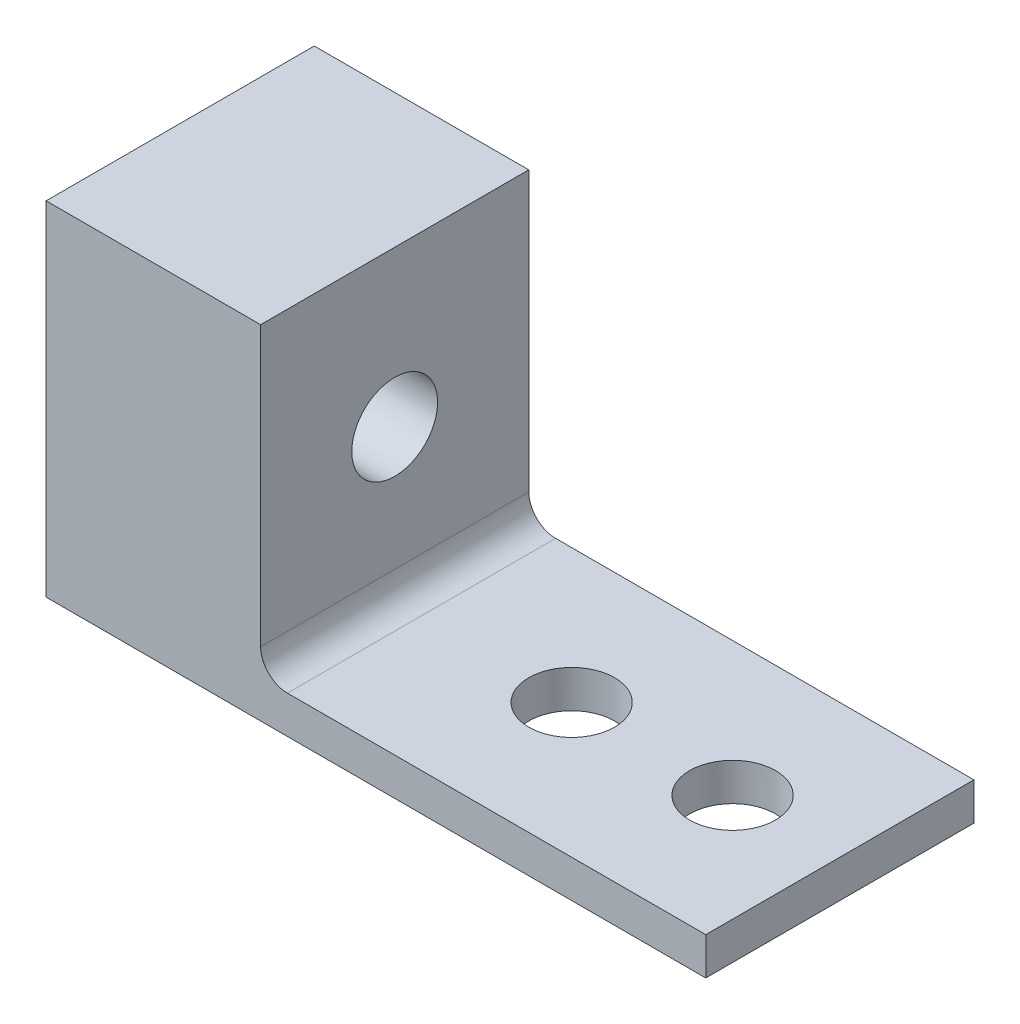
SolidWorks part; units mm, degrees
material "Plain Carbon Steel"
ref_plane "Front Plane" through (0, 0, 0) normal (0, 0, 1) x (1, 0, 0)
ref_plane "Top Plane" through (0, 0, 0) normal (0, 1, 0) x (1, 0, 0)
ref_plane "Right Plane" through (0, 0, 0) normal (1, 0, 0) x (0, 0, -1)
sketch "Sketch1" plane through (0, 0, 0) normal (0, 0, 1) x (1, 0, 0)
  line L0 (0, 0) -> (0, 16.256)
  line L1 (0, 16.256) -> (10.16, 16.256)
  line L2 (10.16, 16.256) -> (10.16, 1.778)
  line L3 (10.16, 1.778) -> (31.242, 1.778)
  line L4 (31.242, 1.778) -> (31.242, 0)
  line L5 (31.242, 0) -> (0, 0)
  dimension "D1" = 10.16
  dimension "D2" = 1.778
  dimension "D3" = 21.082
  dimension "D4" = 16.256
extrude "Boss-Extrude1" add sketch "Sketch1" against normal mid plane 12.7
sketch "Sketch2" plane through (0, 0, 0) normal (-1, 0, 0) x (0, 0, 1)
  circle A0 centre (0, 8.89) radius 2.032
  dimension "D1" = 4.064
  dimension "D2" = 8.89
extrude "Cut-Extrude1" cut sketch "Sketch2" against normal up to next
sketch "Sketch3" plane through (0, 0, 0) normal (0, -1, 0) x (1, 0, 0)
  circle A0 centre (18.542, 0) radius 2.032
  dimension "D1" = 4.064
  dimension "D2" = 8.382
extrude "Cut-Extrude2" cut sketch "Sketch3" against normal up to next
fillet "Fillet2" radius 1.27 1 edges at (10.16, 1.778, 0)
pattern_linear "LPattern1" count 2 spacing 7.62 along (1, 0, 0) of "Cut-Extrude2"
